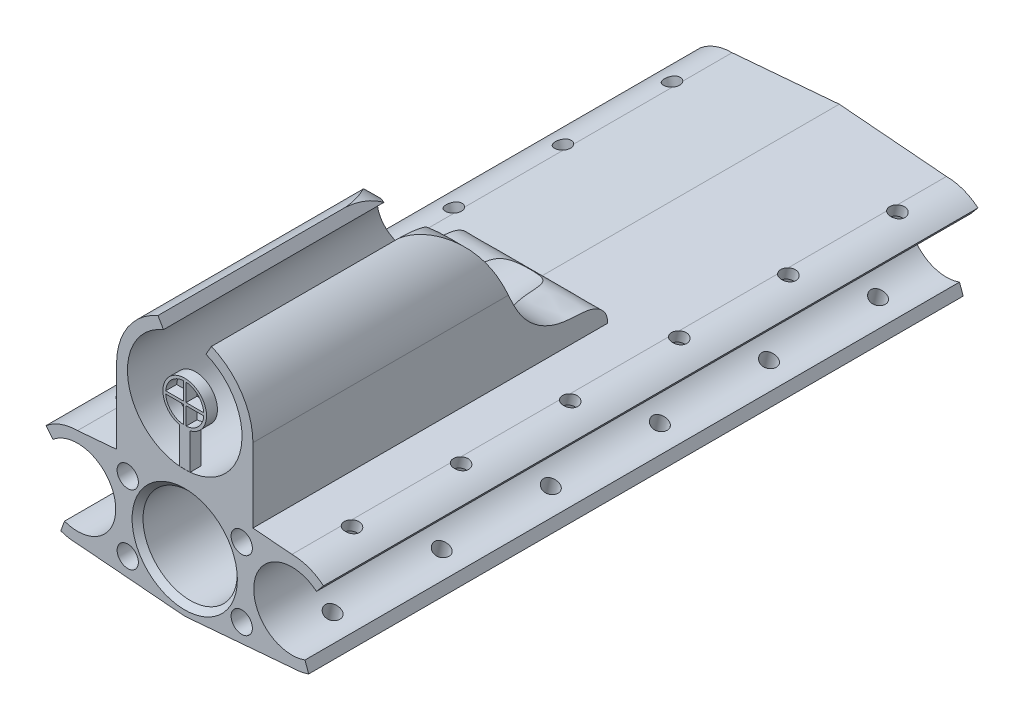
SolidWorks part; units mm, degrees
ref_plane "Front Plane" through (0, 0, 0) normal (0, 0, 1) x (1, 0, 0)
ref_plane "Top Plane" through (0, 0, 0) normal (0, 1, 0) x (1, 0, 0)
ref_plane "Right Plane" through (0, 0, 0) normal (1, 0, 0) x (0, 0, -1)
sketch "Sketch1" plane through (0, 0, 0) normal (0, 0, 1) x (1, 0, 0)
  line L4 (-19.65, 9) -> (0, 10.65)
  line L5 (0, 10.65) -> (19.65, 9)
  line L8 (-19.65, -9) -> (0, -10.65)
  line L9 (0, -10.65) -> (19.65, -9)
  line L11 (14.5665, -7.4269) -> (6.9542, -8.0661)
  line L14 (14.5665, 7.4269) -> (6.9542, 8.0661)
  line L17 (-6.9542, 8.0661) -> (-14.5665, 7.4269)
  line L19 (-6.9542, -8.0661) -> (-14.5665, -7.4269)
  circle A0 centre (0, 0) radius 8.65
  arc A3 (-6.9542, 8.0661) -> (-6.9542, -8.0661) centre (0, 0) ccw
  circle A4 centre (-19.65, 0) radius 7
  arc A5 (-19.65, 9) -> (-19.65, -9) centre (-19.65, 0) ccw
  circle A6 centre (19.65, 0) radius 7
  arc A7 (14.5665, 7.4269) -> (14.5665, -7.4269) centre (19.65, 0) ccw
  arc A8 (1.776, 10.5009) -> (-1.776, 10.5009) centre (0, 0) ccw
  arc A9 (19.65, -9) -> (19.65, 9) centre (19.65, 0) ccw
  arc A10 (-14.5665, -7.4269) -> (-14.5665, 7.4269) centre (-19.65, 0) ccw
  arc A11 (-1.776, -10.5009) -> (1.776, -10.5009) centre (0, 0) ccw
  arc A12 (6.9542, -8.0661) -> (6.9542, 8.0661) centre (0, 0) ccw
  dimension "D1" = 17.3
  dimension "D2" = 21.3
  dimension "D3" = 14
  dimension "D4" = 18
  dimension "D5" = 18
  dimension "D6" = 14
  dimension "D7" = 7.6123
  dimension "D8" = 9.6
  dimension "D9" = 7.6123
  dimension "D10" = 6.9542
  dimension "D11" = 6.9542
  dimension "D12" = 7.6123
  dimension "D13" = 9.6
  dimension "D14" = 7.6123
extrude "Boss-Extrude2" add sketch "Sketch1" along normal mid plane 120 contours L4 L5 A9 L9 L8 A5 | A6 | A0 | A4 | L14 A12 L11 A7
hole_wizard "Ø1.0mm Dowel Hole1" positions "Sketch2" profile "Sketch3" hole size "Ø1.0" standard "ANSI Metric" end condition through all
sketch "Sketch2" plane through (0, 0, -60) normal (0, 0, -1) x (-1, 0, 0)
  point P0 (10.45, 6.3516)
  point P2 (10.45, -6.3516)
  point P4 (-10.45, -6.3516)
  point P6 (-10.45, 6.3516)
  dimension "D1" = 12.7033
  dimension "D2" = 6.3516
  dimension "D3" = 20.9
  dimension "D4" = 10.45
sketch "Sketch3" plane through (-10.45, 6.3516, -60) normal (1, 0, 0) x (0, 1, 0)
  line L0 (0, 0) -> (0, 120)
  line L1 (0, 120) -> (1.95, 120)
  line L2 (1.95, 120) -> (1.95, 0)
  line L5 (1.95, 0) -> (0, 0)
  line L11 (0, -6.35) -> (0, 107.95) construction
  dimension "Thru Hole Dia." = 3.9
  dimension "Thru Hole Depth" = 120
sketch "Sketch5" plane through (0, 0, 0) normal (0, 1, 0) x (1, 0, 0)
  line L0 (19.65, -60) -> (19.65, 60) construction
  line L2 (19.65, -60) -> (28.65, -60) construction
  circle A0 centre (19.65, -45) radius 1.4
  circle A1 centre (19.65, -30) radius 1.4
  circle A2 centre (19.65, 30) radius 1.4
  circle A3 centre (19.65, 15) radius 1.4
  circle A4 centre (19.65, 0) radius 1.4
  circle A5 centre (19.65, -15) radius 1.4
  circle A6 centre (19.65, 45) radius 1.4
  dimension "D1" = 2.8
  dimension "D3" = 15
  dimension "D4" = 15
  dimension "D5" = 15
  dimension "D6" = 15
  dimension "D7" = 15
  dimension "D8" = 15
  dimension "D2" = 15
chamfer "Chamfer1" distance 1 angle 45 2 edges at (8.65, 0, -60) (8.65, 0, 60)
sketch "Sketch7" plane through (0, 0, -60) normal (0, 0, -1) x (-1, 0, 0)
  line L0 (-19.65, 0) -> (-19.65, 9)
  line L1 (-19.65, 0) -> (-21.6746, 8.7693)
  arc A0 (-19.65, 9) -> (-19.65, -9) centre (-19.65, 0) ccw construction
  dimension "D1" = 13
ref_plane "Plane2" through (21.6746, 8.7693, -60) normal (0.225, 0.9744, 0) x (0.9744, -0.225, 0)
sketch "Sketch8" plane through (21.6746, 8.7693, -60) normal (0.225, 0.9744, 0) x (0.9744, -0.225, 0)
  line L0 (-1.0123, 0) -> (-1.0123, -127.3334) construction
  line L1 (0, 0) -> (-2.0246, 0) construction
  line L2 (-2.0246, -120) -> (9, -120) construction
  circle A0 centre (-1.0123, -110) radius 1.4
  circle A1 centre (-1.0123, -90) radius 1.4
  circle A5 centre (-1.0123, -70) radius 1.4
  circle A6 centre (-1.0123, -50) radius 1.4
  circle A7 centre (-1.0123, -30) radius 1.4
  circle A8 centre (-1.0123, -10) radius 1.4
  dimension "D2" = 2.8
  dimension "D4" = 2.8
  dimension "D9" = 2.8
  dimension "D10" = 2.8
  dimension "D11" = 2.8
  dimension "D12" = 2.8
  dimension "D1" = 10
  dimension "D3" = 20
  dimension "D5" = 20
  dimension "D6" = 20
  dimension "D7" = 20
  dimension "D8" = 20
extrude "Cut-Extrude3" cut sketch "Sketch8" against normal mid plane 100 contours A7 | A6 | A5 | A1 | A0 | A8
mirror "Mirror2" about plane through (0, 0, 0) normal (1, 0, 0) of "Cut-Extrude3"
sketch "Sketch10" plane through (0, 0, 60) normal (0, 0, 1) x (1, 0, 0)
  line L0 (-12.5, 23.15) -> (-12.5, 9.6004)
  line L1 (-19.65, 9) -> (0, 10.65) construction
  line L2 (-12.5, 9.6004) -> (0, 10.65)
  line L3 (12.5, 23.15) -> (12.5, 9.6004)
  line L4 (0, 10.65) -> (19.65, 9) construction
  line L5 (12.5, 9.6004) -> (0, 10.65)
  arc A0 (12.5, 23.15) -> (-12.5, 23.15) centre (0, 23.15) ccw
  dimension "D1" = 25
  dimension "D2" = 13.5496
extrude "Boss-Extrude3" add sketch "Sketch10" against normal blind 65 contours A0 L0 L2 L5 L3
sketch "Sketch11" plane through (0, 0, 60) normal (0, 0, 1) x (1, 0, 0)
  circle A0 centre (0, 23.15) radius 10.5
  dimension "D1" = 21
extrude "Cut-Extrude4" cut sketch "Sketch11" against normal blind 65
sketch "Sketch17" plane through (0, 0, 60) normal (0, 0, 1) x (1, 0, 0)
  line L0 (-10.5, 23.15) -> (10.5, 23.15) construction
  line L1 (-1, 12.6977) -> (-1, 19.277)
  line L2 (-1, 19.277) -> (1, 19.277)
  line L3 (0, 33.65) -> (0, 12.65) construction
  line L4 (1, 19.277) -> (1, 12.6977)
  line L5 (1, 12.6977) -> (-1, 12.6977)
  circle A0 centre (0, 23.15) radius 10.5 construction
  circle A1 centre (0, 23.15) radius 4
  circle A2 centre (0, 23.15) radius 3.5
  dimension "D2" = 8
  dimension "D3" = 7
  dimension "D1" = 2
extrude "Boss-Extrude7" add sketch "Sketch17" against normal blind 2 separate body contours A1 L1 L5 L4 | A2
sketch "Sketch18" plane through (0, 0, 60) normal (0, 0, 1) x (1, 0, 0)
  line L0 (0, 23.15) -> (0, 22.901) construction
  line L1 (-3.5, 23.15) -> (-3.65, 23.15) construction
  line L2 (-0.25, 22.901) -> (-0.25, 19.501)
  line L3 (-0.25, 26.801) -> (0.25, 26.801)
  line L4 (-0.25, 26.801) -> (-0.25, 23.401)
  line L5 (-0.25, 19.501) -> (0.25, 19.501)
  line L6 (0.25, 26.801) -> (0.25, 23.401)
  line L7 (-3.65, 23.401) -> (-0.25, 23.401)
  line L8 (-3.65, 23.401) -> (-3.65, 22.901)
  line L9 (-3.65, 22.901) -> (-0.25, 22.901)
  line L10 (3.65, 23.401) -> (3.65, 22.901)
  line L11 (3.65, 23.15) -> (3.5, 23.15) construction
  line L12 (0.25, 23.401) -> (3.65, 23.401)
  line L13 (0.25, 22.901) -> (3.65, 22.901)
  line L14 (0.25, 22.901) -> (0.25, 19.501)
  line L15 (0, 19.501) -> (0, 19.65) construction
  circle A0 centre (0, 23.15) radius 3.5 construction
  dimension "D1" = 0.5
  dimension "D2" = 0.251
  dimension "D3" = 0.5
  dimension "D4" = 0.25
  dimension "D5" = 3.4
  dimension "D6" = 3.4
  dimension "D7" = 3.4
  dimension "D8" = 3.4
extrude "Boss-Extrude11" add sketch "Sketch18" against normal blind 2 contours L7 L4 L3 L6 L12 L10 L13 L14 L5 L2 L9 L8
sketch "Sketch19" plane through (0, 0, 60) normal (0, 0, 1) x (1, 0, 0)
  line L0 (0, 35.65) -> (0, 23.15) construction
  line L1 (0, 26.15) -> (-11.547, 46.15)
  line L2 (-11.547, 46.15) -> (11.547, 46.15)
  line L3 (11.547, 46.15) -> (0, 26.15)
  arc A0 (12.5, 23.15) -> (-12.5, 23.15) centre (0, 23.15) ccw construction
  dimension "D1" = 60
  dimension "D2" = 30
  dimension "D3" = 3
  dimension "D4" = 20
extrude "Cut-Extrude6" cut sketch "Sketch19" against normal blind 100
sketch "Sketch21" plane through (-12.5, 0, 0) normal (-1, 0, 0) x (0, 0, 1)
  line L0 (-5, 10.65) -> (-5, 34.6471)
  line L1 (-5, 23.15) -> (-5, 9.6004) construction
  line L2 (-5, 9.6004) -> (-5, 10.65) construction
  line L3 (-5, 34.6471) -> (27.5, 34.6471)
  line L4 (-5, 34.6471) -> (60, 34.6471) construction
  spline S0 degree 3 poles (-5, 10.65) (-3.4367, 14.3029) (2.9353, 12.6284) (15.8478, 20.1883) (13.9297, 35.1929) (27.5, 34.6471) knots 0 0 0 0 0.227867 0.397942 1 1 1 1
  line M2 (60, 23.15) -> (-5, 23.15)
  line M3 (-5, 23.15) -> (-5, 9.6004)
  dimension "D1" = 2.2194
  dimension "D2" = 6.2368
  dimension "D3" = 6.2368
  dimension "D4" = 3.857
  dimension "D5" = 2.368
  dimension "D6" = 0.9027
  dimension "D7" = 3.4467
  dimension "D8" = 6.6471
  dimension "D9" = 10.6327
extrude "Cut-Extrude10" cut sketch "Sketch21" against normal through all contours S0 M3 M2 | S0 L3 L0 M2
fillet "Fillet2" radius 3 1 edges at (-6.25, 10.65, -5)
sketch "Sketch23" plane through (0, 0, 60) normal (0, 0, 1) x (1, 0, 0)
  line L0 (-19.65, 0) -> (-26.65, 0)
  line L1 (-19.65, 0) -> (-22.0441, -6.5778)
  line L2 (-19.65, 0) -> (-24.1495, 5.3623)
  line L3 (-24.1495, 5.3623) -> (-46.6011, 32.1191)
  line L4 (-46.6011, 32.1191) -> (-46.6011, -74.0476)
  line L5 (-46.6011, -74.0476) -> (-22.0441, -6.5778)
  circle A0 centre (-19.65, 0) radius 7 construction
  arc M13 (-19.65, 9) -> (-19.65, -9) centre (-19.65, 0) ccw
  circle M26 centre (-19.65, 0) radius 7
  dimension "D1" = 120
  dimension "D2" = 50
  dimension "D3" = 106.1666
extrude "Cut-Extrude11" cut sketch "Sketch23" against normal blind 200 contours L0 L2 M26 | L1 L0 M26 | L5 L3 M13 M26 | L4 L5 L3 M13
mirror "Mirror3" about plane through (0, 0, 0) normal (1, 0, 0) of "Cut-Extrude11"
equation "\"D5@Sketch1\"=\"D4@Sketch1\""
equation "\"D6@Sketch1\"=\"D3@Sketch1\""
equation "\"D2@Sketch2\"=\"D1@Sketch2\"/2"
equation "\"D4@Sketch2\"=\"D3@Sketch2\"/2"
equation "\"D4@Sketch5\"=\"D3@Sketch5\""
equation "\"D5@Sketch5\"=\"D4@Sketch5\""
equation "\"D9@Sketch8\"=\"D2@Sketch8\""
equation "\"D10@Sketch8\"=\"D4@Sketch8\""
equation "\"D11@Sketch8\"=\"D4@Sketch8\""
equation "\"D12@Sketch8\"=\"D4@Sketch8\""
equation "\"D4@Sketch8\"=\"D2@Sketch8\""
equation "\"D2@Sketch19\"=\"D1@Sketch19\"/2"
